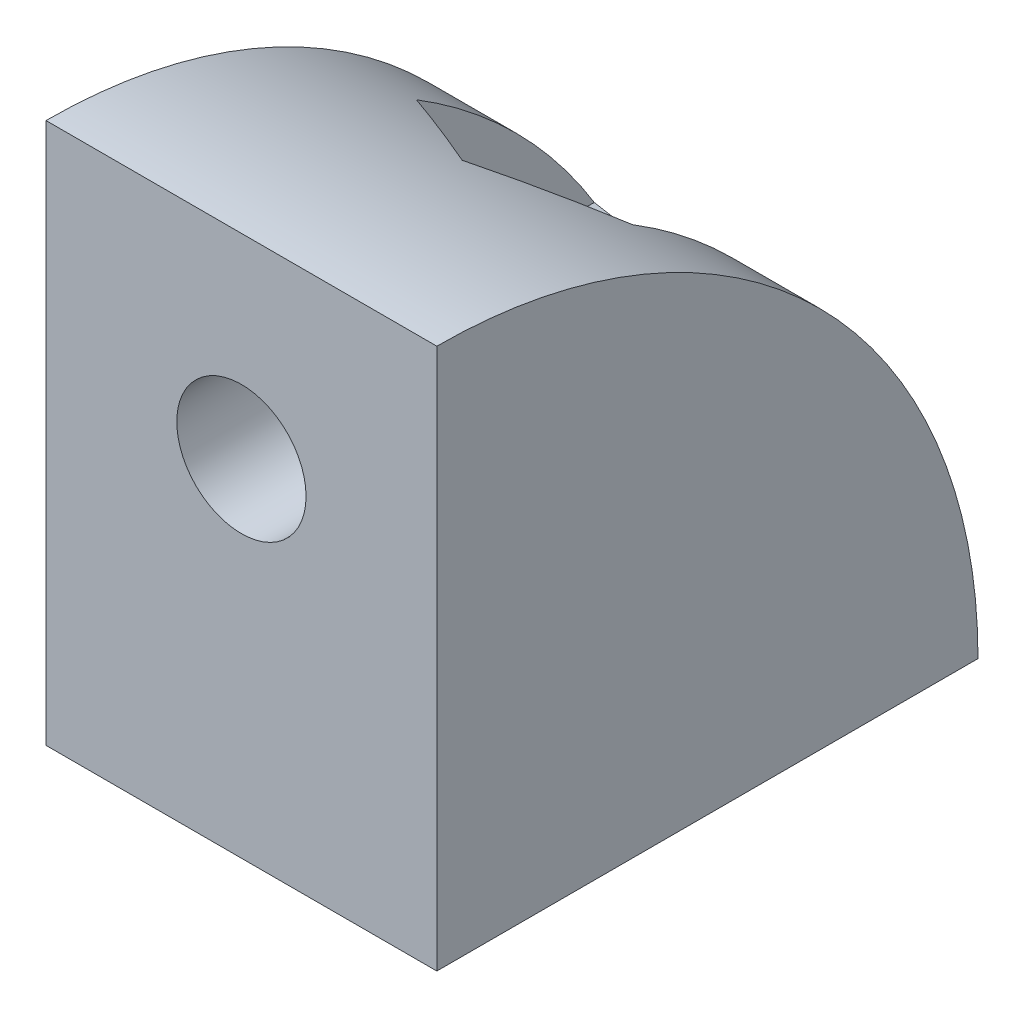
SolidWorks part; units mm, degrees
ref_plane "Спереди" through (0, 0, 0) normal (0, 0, 1) x (1, 0, 0)
ref_plane "Сверху" through (0, 0, 0) normal (0, 1, 0) x (1, 0, 0)
ref_plane "Справа" through (0, 0, 0) normal (1, 0, 0) x (0, 0, -1)
sketch "Sketch2" plane through (0, 0, 0) normal (1, 0, 0) x (0, 0, -1)
  line L1 (0, 0) -> (18, 0)
  line L2 (0, 0) -> (0, 18)
  arc A0 (18, 0) -> (0, 18) centre (0, 0) ccw
  dimension "D2" = 18
  dimension "D1" = 18
extrude "Extrude1" add sketch "Sketch2" along normal blind 13
sketch "Sketch3" plane through (0, 0, 0) normal (0, 0, 1) x (1, 0, 0)
  line L0 (6.5, 11.5) -> (6.5, 18) construction
  line L2 (13, 18) -> (0, 18) construction
  line L3 (13, 18) -> (13, 0) construction
  line L4 (13, 11.5) -> (6.5, 11.5) construction
  circle A0 centre (6.5, 11.5) radius 2.15
  dimension "D1" = 4.3
extrude "Extrude2" cut sketch "Sketch3" against normal blind 30
sketch "Sketch5" plane through (0, 0, 0) normal (0, 0, 1) x (1, 0, 0)
  line L1 (6.5, 15.6569) -> (2.9, 13.5785)
  line L2 (2.9, 13.5785) -> (2.9, 9.4215)
  line L3 (2.9, 9.4215) -> (6.5, 7.3431)
  line L4 (6.5, 7.3431) -> (10.1, 9.4215)
  line L5 (10.1, 9.4215) -> (10.1, 13.5785)
  line L6 (10.1, 13.5785) -> (6.5, 15.6569)
  circle A0 centre (6.5, 11.5) radius 3.6 construction
  dimension "D1" = 7.2
extrude "Extrude3" cut sketch "Sketch5" against normal blind 30 from offset 4 offset against normal yes
ref_plane "Plane1" through (0, 0, 0) normal (0, 0.7071, 0.7071) x (1, 0, 0)
mirror "Mirror1" about plane through (0, 0, 0) normal (0, 0.7071, 0.7071) of "Extrude3", "Extrude2"
equation "\"thickness\"=4"
equation "\"pin_l\"=5"
equation "\"pin_skew\"=4"
equation "\"pin_r\"=5"
equation "\"M4_plastic_thread\"=3.8"
equation "\"M3_plastic_thread\" = 2.8"
equation "\"min_d\"=0.2"
equation "\"M4_hole\"= 4.3"
equation "\"D1@Sketch3\"=\"M4_hole\""
